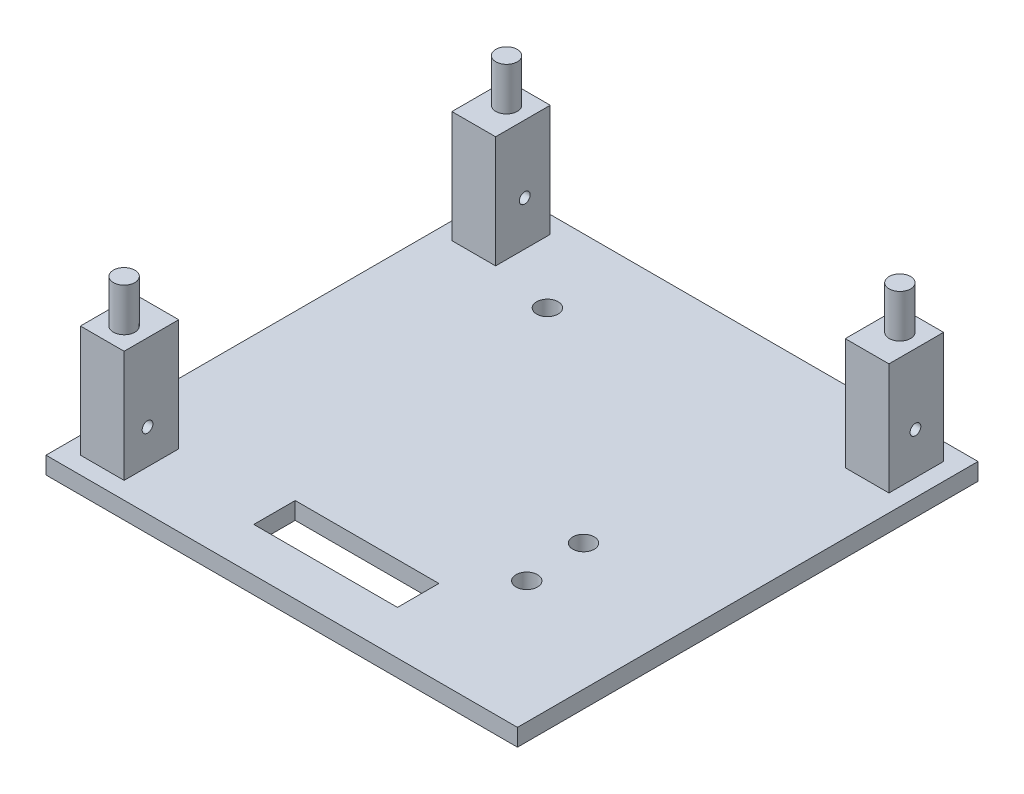
SolidWorks part; units mm, degrees
ref_plane "Front Plane" through (0, 0, 0) normal (0, 0, 1) x (1, 0, 0)
ref_plane "Top Plane" through (0, 0, 0) normal (0, 1, 0) x (1, 0, 0)
ref_plane "Right Plane" through (0, 0, 0) normal (1, 0, 0) x (0, 0, -1)
sketch "Sketch2" plane through (0, 0, 0) normal (0, 1, 0) x (1, 0, 0)
  line L1 (27.4, -26.765) -> (-27.4, -26.765)
  line L2 (27.4, -26.765) -> (27.4, 26.765)
  line L3 (27.4, 26.765) -> (-27.4, 26.765)
  line L4 (-27.4, -26.765) -> (-27.4, 26.765)
  line L5 (27.4, -26.765) -> (-27.4, 26.765) construction
  line L6 (27.4, 26.765) -> (-27.4, -26.765) construction
  point P0 (0, 0)
  dimension "D1" = 54.8
  dimension "D2" = 53.53
extrude "Boss-Extrude1" add sketch "Sketch2" along normal blind 2
sketch "Sketch3" plane through (0, 2, 0) normal (0, 1, 0) x (1, 0, 0)
  line L0 (27.4, 26.765) -> (-27.4, 26.765) construction
  line L1 (-20.32, 18.415) -> (-25.4, 18.415)
  line L2 (-20.32, 18.415) -> (-20.32, 24.765)
  line L3 (-20.32, 24.765) -> (-25.4, 24.765)
  line L4 (-25.4, 18.415) -> (-25.4, 24.765)
  line L5 (-20.32, 18.415) -> (-25.4, 24.765) construction
  line L6 (-20.32, 24.765) -> (-25.4, 18.415) construction
  line L7 (-27.4, 26.765) -> (-27.4, -26.765) construction
  line L8 (27.4, -26.765) -> (27.4, 26.765) construction
  line L9 (25.4, 18.415) -> (20.32, 18.415)
  line L10 (25.4, 18.415) -> (25.4, 24.765)
  line L11 (25.4, 24.765) -> (20.32, 24.765)
  line L12 (20.32, 18.415) -> (20.32, 24.765)
  line L13 (25.4, 18.415) -> (20.32, 24.765) construction
  line L14 (25.4, 24.765) -> (20.32, 18.415) construction
  line L15 (-27.4, -26.765) -> (27.4, -26.765) construction
  line L16 (-20.32, -24.765) -> (-25.4, -24.765)
  line L17 (-20.32, -24.765) -> (-20.32, -18.415)
  line L18 (-20.32, -18.415) -> (-25.4, -18.415)
  line L19 (-25.4, -24.765) -> (-25.4, -18.415)
  line L20 (-20.32, -24.765) -> (-25.4, -18.415) construction
  line L21 (-20.32, -18.415) -> (-25.4, -24.765) construction
  point P0 (-22.86, 21.59)
  point P7 (22.86, 21.59)
  point P16 (-22.86, -21.59)
  dimension "D1" = 2
  dimension "D2" = 2
  dimension "D3" = 5.08
  dimension "D4" = 6.35
  dimension "D5" = 5.08
  dimension "D6" = 6.35
  dimension "D7" = 2
  dimension "D8" = 2
  dimension "D9" = 2
  dimension "D10" = 2
  dimension "D11" = 5.08
  dimension "D12" = 6.35
extrude "Boss-Extrude2" add sketch "Sketch3" along normal blind 13
sketch "Sketch6" plane through (0, 15, 0) normal (0, 1, 0) x (1, 0, 0)
  line L0 (25.4, 24.765) -> (20.32, 24.765) construction
  line L2 (-20.32, 24.765) -> (-25.4, 24.765) construction
  line L3 (-25.4, 24.765) -> (-25.4, 18.415) construction
  line L4 (20.32, 24.765) -> (20.32, 18.415) construction
  line L6 (-20.32, -24.765) -> (-20.32, -18.415) construction
  line L8 (-25.4, -24.765) -> (-20.32, -24.765) construction
  circle A0 centre (-22.86, 22.225) radius 1.25
  circle A1 centre (22.86, 22.225) radius 1.25
  circle A2 centre (-22.86, -22.225) radius 1.25
  point P4 (-22.86, 24.765)
  point P17 (-22.86, -24.765)
  point P19 (22.86, 24.765)
  dimension "D1" = 2.54
  dimension "D3" = 2.54
  dimension "D5" = 2.54
  dimension "D2" = 2.54
  dimension "D4" = 2.54
  dimension "D6" = 2.54
extrude "Boss-Extrude3" add sketch "Sketch6" along normal blind 5
sketch "Sketch7" plane through (0, 0, 0) normal (0, -1, 0) x (-1, 0, 0)
  line L1 (8.3496, -21.6623) -> (-8.3496, -21.6623)
  line L2 (8.3496, -21.6623) -> (8.3496, -16.8477)
  line L3 (8.3496, -16.8477) -> (-8.3496, -16.8477)
  line L4 (-8.3496, -21.6623) -> (-8.3496, -16.8477)
  line L5 (8.3496, -21.6623) -> (-8.3496, -16.8477) construction
  line L6 (8.3496, -16.8477) -> (-8.3496, -21.6623) construction
  point P0 (0, -19.255)
extrude "Cut-Extrude1" cut sketch "Sketch7" against normal up to next
sketch "Sketch8" plane through (0, 0, 0) normal (0, -1, 0) x (1, 0, 0)
  circle A0 centre (12.6874, 4.3711) radius 1.25
  circle A1 centre (-13.0827, -17.1974) radius 1.25
extrude "Cut-Extrude2" cut sketch "Sketch8" against normal up to next
sketch "Sketch9" plane through (-25.4, 0, 0) normal (-1, 0, 0) x (0, 0, 1)
  circle A1 centre (-21.8045, 7.1574) radius 0.625
extrude "Cut-Extrude4" cut sketch "Sketch9" against normal up to next
sketch "Sketch10" plane through (25.4, 0, 0) normal (1, 0, 0) x (0, 0, -1)
  circle A0 centre (21.4936, 6.854) radius 0.625
extrude "Cut-Extrude5" cut sketch "Sketch10" against normal up to next
sketch "Sketch11" plane through (-25.4, 0, 0) normal (-1, 0, 0) x (0, 0, 1)
  circle A0 centre (22.0455, 6.0227) radius 0.625
extrude "Cut-Extrude6" cut sketch "Sketch11" against normal up to next
sketch "Sketch12" plane through (0, 2, 0) normal (0, 1, 0) x (1, 0, 0)
  circle A0 centre (13.1906, -11.4753) radius 1.25
extrude "Cut-Extrude7" cut sketch "Sketch12" against normal up to next
